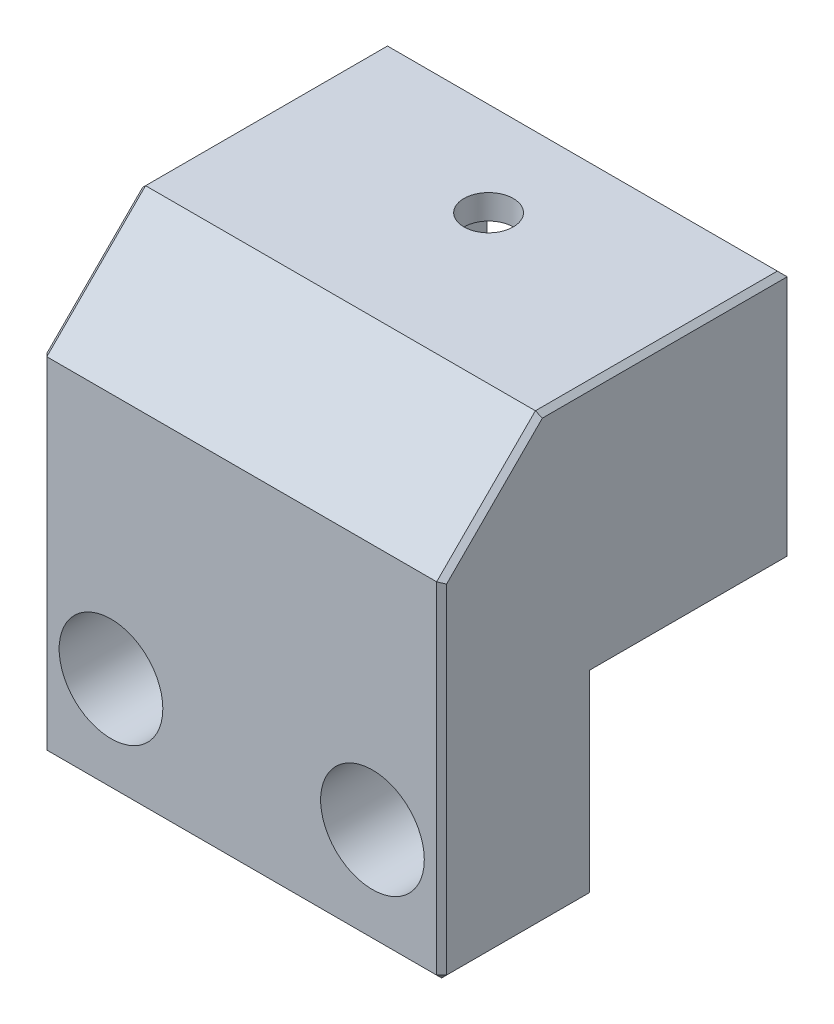
SolidWorks part; units mm, degrees
ref_plane "Front Plane" through (0, 0, 0) normal (0, 0, 1) x (1, 0, 0)
ref_plane "Top Plane" through (0, 0, 0) normal (0, 1, 0) x (1, 0, 0)
ref_plane "Right Plane" through (0, 0, 0) normal (1, 0, 0) x (0, 0, -1)
sketch "Sketch1" plane through (0, 0, 0) normal (0, 1, 0) x (1, 0, 0)
  line L0 (0, 0) -> (-20.24, 0) construction
  line L2 (-20.24, 10) -> (20.24, 10)
  line L3 (-20.24, 10) -> (-20.24, -10)
  line L4 (-20.24, -10) -> (20.24, -10)
  line L5 (20.24, 10) -> (20.24, -10)
  line L6 (-20.24, 10) -> (20.24, -10) construction
  line L7 (-20.24, -10) -> (20.24, 10) construction
  circle A0 centre (0, 0) radius 2.5
  point P3 (0, 0)
  point P9 (-16.3857, -10)
  point P10 (0, 0)
  dimension "D1" = 5
  dimension "D2" = 20
  dimension "D3" = 20.24
extrude "Boss-Extrude1" add sketch "Sketch1" along normal blind 25
sketch "Sketch9" plane through (0, 0, 10) normal (0, 0, 1) x (1, 0, 0)
  line L1 (-20.24, 25) -> (20.24, 25)
  line L2 (-20.24, 25) -> (-20.24, -20)
  line L3 (-20.24, -20) -> (20.24, -20)
  line L4 (20.24, 25) -> (20.24, -20)
  line L5 (20.24, 25) -> (20.24, 0) construction
  line L6 (-20.24, 0) -> (20.24, 0) construction
  dimension "D1" = 20
extrude "Boss-Extrude4" add sketch "Sketch9" along normal blind 15
sketch "Sketch10" plane through (0, 25, 0) normal (0, 1, 0) x (1, 0, 0)
  line L0 (10.16, 0) -> (10.16, 10)
  line L1 (20.24, 10) -> (-20.24, 10) construction
  line L2 (10.16, 10) -> (-10.16, 10)
  line L3 (-10.16, 10) -> (-10.16, 0)
  arc A0 (10.16, 0) -> (-10.16, 0) centre (0, 0) cw
  point P9 (-10.9794, -0.8586)
  dimension "D1" = 10.16
extrude "Cut-Extrude2" cut sketch "Sketch10" against normal blind 19.5 from offset 2.5 offset against normal yes
chamfer "Chamfer1" distance 10 angle 45 1 edges at (0, 25, 25)
sketch "Sketch11" plane through (0, 0, 25) normal (0, 0, 1) x (1, 0, 0)
  line L0 (-20.24, -10) -> (20.24, -10) construction
  line L1 (20.24, -20) -> (20.24, 15) construction
  line L2 (-20.24, 15) -> (-20.24, -20) construction
  line L3 (-20.24, -20) -> (20.24, -20) construction
  circle A0 centre (-13.24, -10) radius 7
  circle A1 centre (13.24, -10) radius 7
  point P12 (0, 0)
  dimension "D2" = 14
  dimension "D1" = 10
hole_wizard "CBORE for M5 SBHCS1" positions "Sketch12" profile "Sketch13" counterbore size "M5" standard "ANSI Metric" end condition through all
sketch "Sketch12" plane through (0, 0, 25) normal (0, 0, 1) x (1, 0, 0)
  point P0 (-13.24, -10)
  point P3 (13.24, -10)
sketch "Sketch13" plane through (-13.24, -10, 25) normal (1, 0, 0) x (0, -1, 0)
  line L0 (0, 0) -> (0, 35)
  line L1 (0, 35) -> (2.75, 35)
  line L3 (2.75, 35) -> (2.75, 9.75)
  line L4 (2.75, 9.75) -> (5.25, 9.75)
  line L5 (5.25, 9.75) -> (5.25, 0)
  line L7 (5.25, 0) -> (0, 0)
  line L11 (0, -6.35) -> (0, 107.95) construction
  dimension "Thru Hole Dia." = 5.5
  dimension "Thru Hole Depth" = 35
  dimension "C'Bore Dia." = 10.5
  dimension "C'Bore Depth" = 9.75
chamfer "Chamfer2" distance 0.5 angle 45 10 edges at (20.24, -20, 17.5) (-20.24, -20, 17.5) (20.24, 20, 20) (20.24, 25, 2.5) (0, 25, -10) (-20.24, 25, 2.5) (-20.24, 20, 20) (20.24, -2.5, 25) (0, -20, 25) (-20.24, -2.5, 25)
